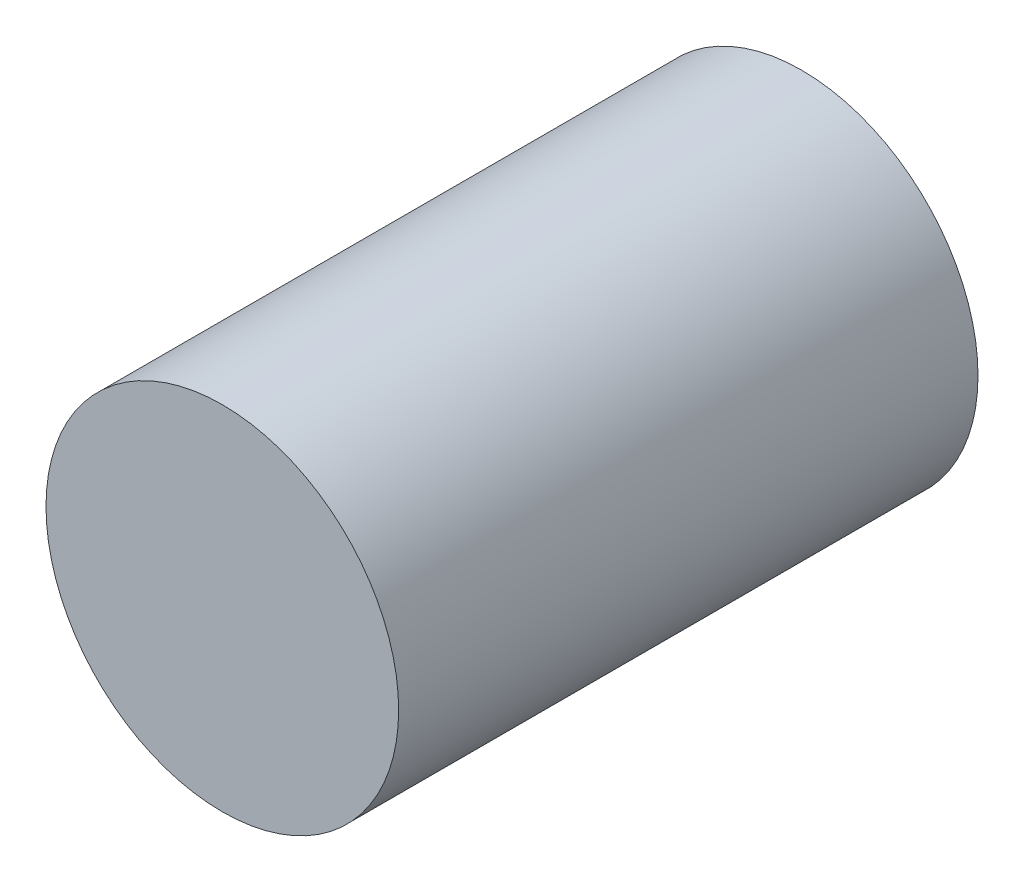
SolidWorks part; units mm, degrees
ref_plane "Front Plane" through (0, 0, 0) normal (0, 0, 1) x (1, 0, 0)
ref_plane "Top Plane" through (0, 0, 0) normal (0, 1, 0) x (1, 0, 0)
ref_plane "Right Plane" through (0, 0, 0) normal (1, 0, 0) x (0, 0, -1)
sketch "Sketch1" plane through (0, 0, 0) normal (0, 0, 1) x (1, 0, 0)
  circle A0 centre (0, 0) radius 7
  dimension "D1" = 14
extrude "Boss-Extrude1" add sketch "Sketch1" along normal blind 23 contours A0
